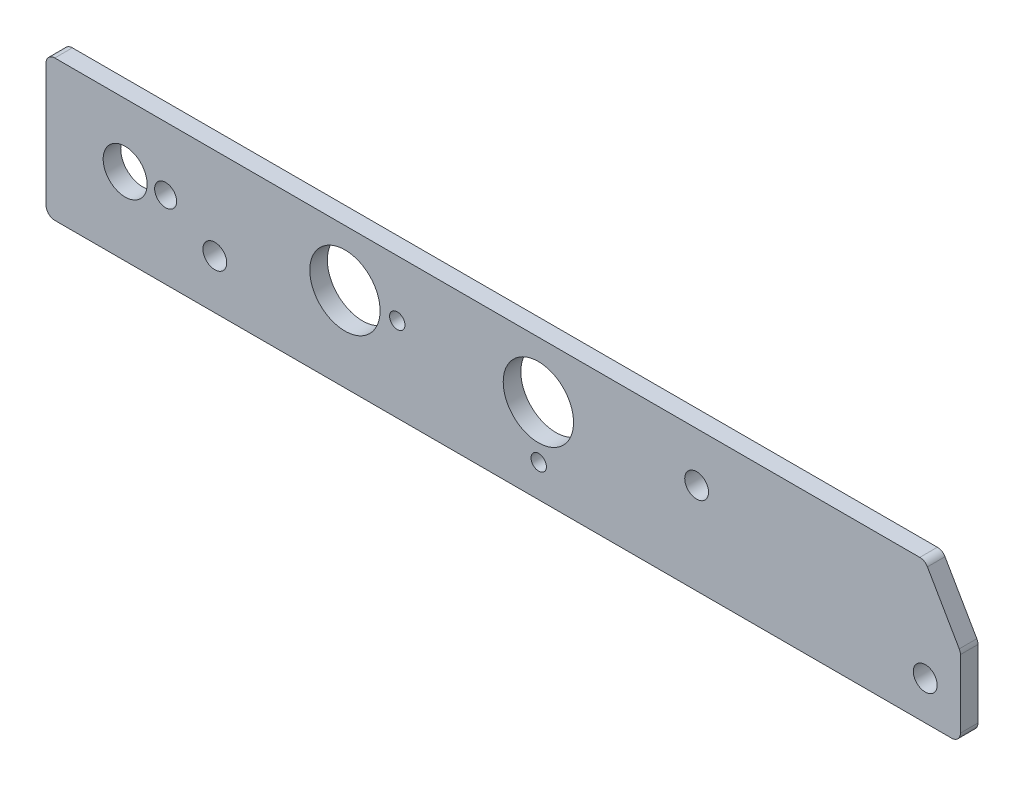
SolidWorks part; units mm, degrees
material "Acrylic (Medium-high impact)"
ref_plane "Front Plane" through (0, 0, 0) normal (0, 0, 1) x (1, 0, 0)
ref_plane "Top Plane" through (0, 0, 0) normal (0, 1, 0) x (1, 0, 0)
ref_plane "Right Plane" through (0, 0, 0) normal (1, 0, 0) x (0, 0, -1)
sketch "Sketch1" plane through (0, 0, 0) normal (0, 0, 1) x (1, 0, 0)
  line L5 (157.7677, 0) -> (1.5875, 0)
  line L6 (0, -1.5875) -> (0, -23.8125)
  line L7 (1.5875, -25.4) -> (163.5125, -25.4)
  line L8 (165.1, -23.8125) -> (165.1, -11.5379)
  line L9 (164.8873, -10.7441) -> (159.1425, -0.7937)
  line L10 (157.7677, 0) -> (1.5875, 0)
  line L11 (0, -1.5875) -> (0, -23.8125)
  line L12 (1.5875, -25.4) -> (163.5125, -25.4)
  line L13 (165.1, -23.8125) -> (165.1, -11.5379)
  line L14 (164.8873, -10.7441) -> (159.1425, -0.7937)
  arc A5 (159.1425, -0.7937) -> (157.7677, 0) centre (157.7677, -1.5875) ccw
  arc A6 (1.5875, 0) -> (0, -1.5875) centre (1.5875, -1.5875) ccw
  arc A7 (0, -23.8125) -> (1.5875, -25.4) centre (1.5875, -23.8125) ccw
  arc A8 (163.5125, -25.4) -> (165.1, -23.8125) centre (163.5125, -23.8125) ccw
  arc A9 (165.1, -11.5379) -> (164.8873, -10.7441) centre (163.5125, -11.5379) ccw
  arc A10 (159.1425, -0.7937) -> (157.7677, 0) centre (157.7677, -1.5875) ccw
  arc A11 (1.5875, 0) -> (0, -1.5875) centre (1.5875, -1.5875) ccw
  arc A12 (0, -23.8125) -> (1.5875, -25.4) centre (1.5875, -23.8125) ccw
  arc A13 (163.5125, -25.4) -> (165.1, -23.8125) centre (163.5125, -23.8125) ccw
  arc A14 (165.1, -11.5379) -> (164.8873, -10.7441) centre (163.5125, -11.5379) ccw
  dimension "D1" = 0
extrude "Boss-Extrude1" add sketch "Sketch1" along normal blind 3.175
hole_wizard "1/2 (0.5) Diameter Hole1" positions "Sketch3" profile "Sketch2" hole size "1/2" standard "ANSI Inch" end condition through all
sketch "Sketch3" plane through (0, 0, 0) normal (0, 0, -1) x (-1, 0, 0)
  point P0 (-53.975, -10.16)
  point P3 (-88.9, -10.16)
sketch "Sketch2" plane through (53.975, -10.16, 0) normal (1, 0, 0) x (0, 1, 0)
  line L0 (0, 0) -> (0, 3.175)
  line L1 (0, 3.175) -> (6.35, 3.175)
  line L2 (6.35, 3.175) -> (6.35, 0)
  line L5 (6.35, 0) -> (0, 0)
  line L11 (0, -6.35) -> (0, 107.95) construction
  dimension "Thru Hole Dia." = 12.7
  dimension "Thru Hole Depth" = 3.175
hole_wizard "5/16 (0.3125) Diameter Hole1" positions "Sketch5" profile "Sketch4" hole size "5/16" standard "ANSI Inch" end condition through all
sketch "Sketch5" plane through (0, 0, 0) normal (0, 0, -1) x (-1, 0, 0)
  point P0 (-14.2875, -11.43)
sketch "Sketch4" plane through (14.2875, -11.43, 0) normal (1, 0, 0) x (0, 1, 0)
  line L0 (0, 0) -> (0, 3.175)
  line L1 (0, 3.175) -> (3.9688, 3.175)
  line L2 (3.9688, 3.175) -> (3.9688, 0)
  line L5 (3.9688, 0) -> (0, 0)
  line L11 (0, -6.35) -> (0, 107.95) construction
  dimension "Thru Hole Dia." = 7.9375
  dimension "Thru Hole Depth" = 3.175
hole_wizard "5/32 (0.15625) Diameter Hole1" positions "Sketch7" profile "Sketch6" hole size "5/32" standard "ANSI Inch" end condition through all
sketch "Sketch7" plane through (0, 0, 0) normal (0, 0, -1) x (-1, 0, 0)
  point P0 (-21.5983, -11.43)
sketch "Sketch6" plane through (21.5983, -11.43, 0) normal (1, 0, 0) x (0, 1, 0)
  line L0 (0, 0) -> (0, 3.175)
  line L1 (0, 3.175) -> (1.9844, 3.175)
  line L2 (1.9844, 3.175) -> (1.9844, 0)
  line L5 (1.9844, 0) -> (0, 0)
  line L11 (0, -6.35) -> (0, 107.95) construction
  dimension "Thru Hole Dia." = 3.9688
  dimension "Thru Hole Depth" = 3.175
hole_wizard "7/64 (0.10938) Diameter Hole1" positions "Sketch9" profile "Sketch8" hole size "7/64" standard "ANSI Inch" end condition through all
sketch "Sketch9" plane through (0, 0, 0) normal (0, 0, -1) x (-1, 0, 0)
  point P0 (-88.9595, -19.5375)
  point P2 (-63.4234, -10.16)
sketch "Sketch8" plane through (88.9595, -19.5375, 0) normal (1, 0, 0) x (0, 1, 0)
  line L0 (0, 0) -> (0, 3.175)
  line L1 (0, 3.175) -> (1.3891, 3.175)
  line L2 (1.3891, 3.175) -> (1.3891, 0)
  line L5 (1.3891, 0) -> (0, 0)
  line L11 (0, -6.35) -> (0, 107.95) construction
  dimension "Thru Hole Dia." = 2.7783
  dimension "Thru Hole Depth" = 3.175
hole_wizard "#6 Clearance Hole1" positions "Sketch11" profile "Sketch10" hole size "#6" standard "ANSI Inch" end condition through all
sketch "Sketch11" plane through (0, 0, 0) normal (0, 0, -1) x (-1, 0, 0)
  point P0 (-158.75, -18.415)
  point P3 (-117.475, -8.89)
  point P6 (-30.48, -16.51)
sketch "Sketch10" plane through (158.75, -18.415, 0) normal (1, 0, 0) x (0, 1, 0)
  line L0 (0, 0) -> (0, 3.175)
  line L1 (0, 3.175) -> (2.1526, 3.175)
  line L2 (2.1526, 3.175) -> (2.1526, 0)
  line L5 (2.1526, 0) -> (0, 0)
  line L11 (0, -6.35) -> (0, 107.95) construction
  dimension "Thru Hole Dia." = 4.3053
  dimension "Thru Hole Depth" = 3.175
